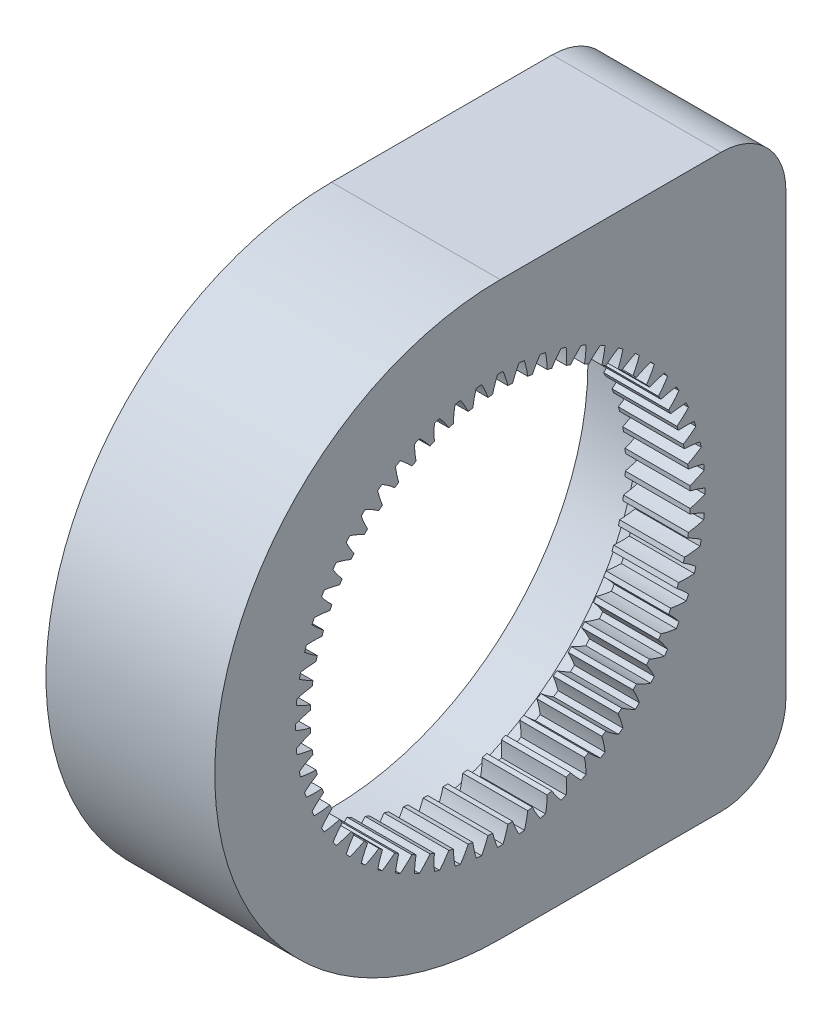
SolidWorks part; units mm, degrees
ref_plane "Plane1" through (0, 0, 0) normal (0, 0, 1) x (1, 0, 0)
ref_plane "Plane2" through (0, 0, 0) normal (0, 1, 0) x (1, 0, 0)
ref_plane "Plane3" through (0, 0, 0) normal (1, 0, 0) x (0, 0, -1)
other "Configuration Table"
sketch "HoldingSke" plane through (0, 0, 0) normal (0, 1, 0) x (1, 0, 0)
  line L0 (0, 0) -> (0.495, -0.8575)
  line L1 (-15, 0) -> (100, 0) construction
  line L2 (0, 0) -> (-2.1039, 2.3779)
  line L3 (0, 0) -> (-11.863, 4.5341)
  line L4 (0, 0) -> (4.318, 7.479)
  line L5 (0, 0) -> (-23.7986, -8.8762)
  line L6 (0, 0) -> (-10.5278, -7.1032)
  line L7 (-2.1039, 2.3779) -> (3.3635, 27.1825)
  line L8 (-76.2, 3.3879) -> (-54.61, 3.3879)
  line L9 (-67.7845, 28.3722) -> (-49.3413, 33.142)
  line L10 (-76.2, 71.12) -> (104.1128, 71.12)
  line L11 (0, 0) -> (-10, 0)
  line L12 (-76.2, 101.6) -> (-76.162, 101.6)
  line L13 (24.9733, 27.94) -> (52.9518, 28.4284)
  line L14 (24.9733, 27.94) -> (24.9743, 27.94)
  line L15 (24.9733, 27.94) -> (100.4006, 29.5858)
  circle A0 centre (0, 0) radius 44
  circle A1 centre (0, 0) radius 12.7
  circle A2 centre (0, 0) radius 12.7
  dimension "Num_teeth" = 60
  dimension "Pitch_radius" = 180.3128
  dimension "Width" = 10
  dimension "Diameter" = 88
sketch "BasProSke" plane through (0, 0, 0) normal (0, 1, 0) x (1, 0, 0)
  line L0 (-10, 0) -> (60, 0) construction
  line L1 (0, 29.29) -> (0, 44)
  line L2 (0, 29.29) -> (10, 29.29)
  line L3 (10, 29.29) -> (10, 44)
  line L4 (10, 44) -> (0, 44)
  dimension "Thickness" = 10
  dimension "Diameter" = 88
revolve "Base-Revolve" add sketch "BasProSke" angle 360 about L0
sketch "TooCutSke" plane through (0, 0, 0) normal (1, 0, 0) x (0, 0, -1)
  line L3 (0.8882, 30.287) -> (0.8882, 53.6633) construction
  line L4 (0, 0) -> (0, 59.563) construction
  line L5 (0, 0) -> (-3.576, 68.2339) construction
  line L6 (-13.5593, 25.727) -> (36.4092, 28.3457) construction
  circle A0 centre (0, 0) radius 30.3 construction
  circle A1 centre (0, 0) radius 31.5635 construction
  circle A2 centre (0, 0) radius 26.4014 construction
  circle A3 centre (0, 0) radius 29.2646 construction
  arc A4 (1.1776, 29.2409) -> (0.4225, 31.5607) centre (-13.5593, 25.727) ccw
  arc A5 (1.1776, 29.2409) -> (-1.1776, 29.2409) centre (0, 0) ccw
  arc A6 (0.4225, 31.5607) -> (-0.4225, 31.5607) centre (0, 0) ccw
  arc A7 (-0.4225, 31.5607) -> (-1.1776, 29.2409) centre (13.5593, 25.727) ccw
extrude "ToothCut" cut sketch "TooCutSke" along normal through all
fillet "Breaks" [suppressed] radius 0.101
fillet "RootFillets" [suppressed] radius 0.2535
pattern_circular "TeethCuts" count 60 every 6 about axis through (-10, 0, 0) along (1, 0, 0) of "RootFillets", "Breaks", "ToothCut"
sketch "Sketch4" plane through (0, 0, 0) normal (-1, 0, 0) x (0, 0, 1)
  circle A0 centre (0, 0) radius 44
  circle A1 centre (0, 0) radius 39.5
  circle A2 centre (0, 0) radius 44 construction
  dimension "D1" = 79
extrude "Boss-Extrude3" add sketch "Sketch4" along normal blind 16
sketch "Sketch7" plane through (10, 0, 0) normal (1, 0, 0) x (0, 0, -1)
  line L0 (0, 44) -> (44, 44)
  line L1 (44, 44) -> (44, 0)
  circle A0 centre (0, 0) radius 44 construction
  arc A1 (44, 0) -> (0, 44) centre (0, 0) ccw
extrude "Boss-Extrude5" add sketch "Sketch7" against normal up to surface (26 mm away) up to face at (-16, 0, 44)
sketch "Sketch10" plane through (10, 0, 0) normal (1, 0, 0) x (0, 0, -1)
  line L0 (0, -44) -> (44, -44)
  line L1 (44, -44) -> (44, 0)
  line L2 (44, 0) -> (44, 44) construction
  circle A0 centre (0, 0) radius 44 construction
  arc A1 (0, -44) -> (44, 0) centre (0, 0) ccw
  dimension "D1" = 180
extrude "Boss-Extrude6" add sketch "Sketch10" against normal up to surface (26 mm away) up to face at (-16, 11.6291, -11.6291)
fillet "Fillet1" radius 10 2 edges at (-3, 44, -44) (-3, -44, -44)
sketch "Sketch14" plane through (0, 0, 0) normal (-1, 0, 0) x (0, 0, 1)
  circle A0 centre (0, 0) radius 37.5
  circle A1 centre (0, 0) radius 39.5 construction
  circle A2 centre (0, 0) radius 39.5
  dimension "D1" = 2
extrude "Boss-Extrude7" add sketch "Sketch14" along normal blind 6
equation "' \"Module@HoldingSke\" = 6.35"
equation "' \"Num_teeth@HoldingSke\" = 24"
equation "' \"Ap@HoldingSke\" =  14.5"
equation "' \"Ap@HoldingSke\" = 14.5"
equation "' \"Width@HoldingSke\" = 12"
equation "' \"Diameter@HoldingSke\" = 8 * 25.4"
equation "' \"Show_teeth@HoldingSke\" = 100"
equation "' \"Backlash@HoldingSke\" = 0.009 * 25.4"
equation "' \"Addendum_fac@HoldingSke\" = 1.0"
equation "' \"Dedendum_fac@HoldingSke\" = 1.25"
equation "' \"Dedendum_add@HoldingSke\" = 0.00005 * 25.4"
equation "' \"Clearance_fac@HoldingSke\" = 0.25"
equation "\"Pitch@HoldingSke\" = 1 / \"Module@HoldingSke\" "
equation "\"Overcut_dia@TooCutSke\" = (\"Num_teeth@HoldingSke\" - 2 * \"Addendum_fac@HoldingSke\") / \"Pitch@HoldingSke\" - 0.002 * 25.4"
equation "\"Pitch_dia@TooCutSke\" = \"Num_teeth@HoldingSke\" / \"Pitch@HoldingSke\""
equation "\"Base_dia@TooCutSke\" = \"Num_teeth@HoldingSke\" / \"Pitch@HoldingSke\" * cos((\"Ap@HoldingSke\"  * 3.14159265 / 180)) * 0.90"
equation "\"Root_dia@TooCutSke\" = \"Num_teeth@HoldingSke\"  / \"Pitch@HoldingSke\" + 2 *  \"Dedendum_fac@HoldingSke\"/ \"Pitch@HoldingSke\" + \"Dedendum_add@HoldingSke\" * 2"
equation "\"Half_ang@TooCutSke\" = 180 / \"Num_teeth@HoldingSke\""
equation "\"Half_CT@TooCutSke\" = \"Num_teeth@HoldingSke\" / \"Pitch@HoldingSke\" * sin((3.14159265 / 2 / \"Num_teeth@HoldingSke\")) / 2 + 10 * \"Backlash@HoldingSke\" / 4"
equation "\"Flank_rad@TooCutSke\" = \"Num_teeth@HoldingSke\" / \"Pitch@HoldingSke\" / 4"
equation "\"Radius@RootFillets\"= \"Clearance_fac@HoldingSke\" / \"Pitch@HoldingSke\" + \"Dedendum_add@HoldingSke\""
equation "\"Break_rad@Breaks\" = 0.02 / \"Pitch@HoldingSke\" * 5"
equation "\"Num_teeth@TeethCuts\" = int( \"Show_teeth@HoldingSke\" ) + 1"
equation "\"Num_teeth@TeethCuts\" = ((sgn( \"Num_teeth@TeethCuts\" - \"Num_teeth@HoldingSke\" )-1)*( \"Num_teeth@TeethCuts\" - \"Num_teeth@HoldingSke\" ))/-2+ \"Num_teeth@HoldingSke\""
equation "\"Num_teeth@TeethCuts\" = ((sgn( \"Num_teeth@TeethCuts\" - 2.0)+1)*( \"Num_teeth@TeethCuts\" - 2.0))/2 +2.0"
equation "\"Angle@TeethCuts\" = 360.0 / \"Num_teeth@HoldingSke\""
equation "\"Diameter@BasProSke\" = \"Num_teeth@HoldingSke\"  / \"Pitch@HoldingSke\" + 2 *  \"Dedendum_fac@HoldingSke\"/ \"Pitch@HoldingSke\" + \"Dedendum_add@HoldingSke\" * 2 + 0.002 * 25.4"
equation "\"Diameter@BasProSke\" = ((sgn( \"Diameter@BasProSke\"  - \"Diameter@HoldingSke\" )+1)*( \"Diameter@BasProSke\"  - \"Diameter@HoldingSke\" ))/2 + \"Diameter@HoldingSke\""
equation "\"Inside_diameter@BasProSke\" =  (\"Num_teeth@HoldingSke\" - 2 * \"Addendum_fac@HoldingSke\") / \"Pitch@HoldingSke\" "
equation "\"Thickness@BasProSke\"  = \"Width@HoldingSke\""
